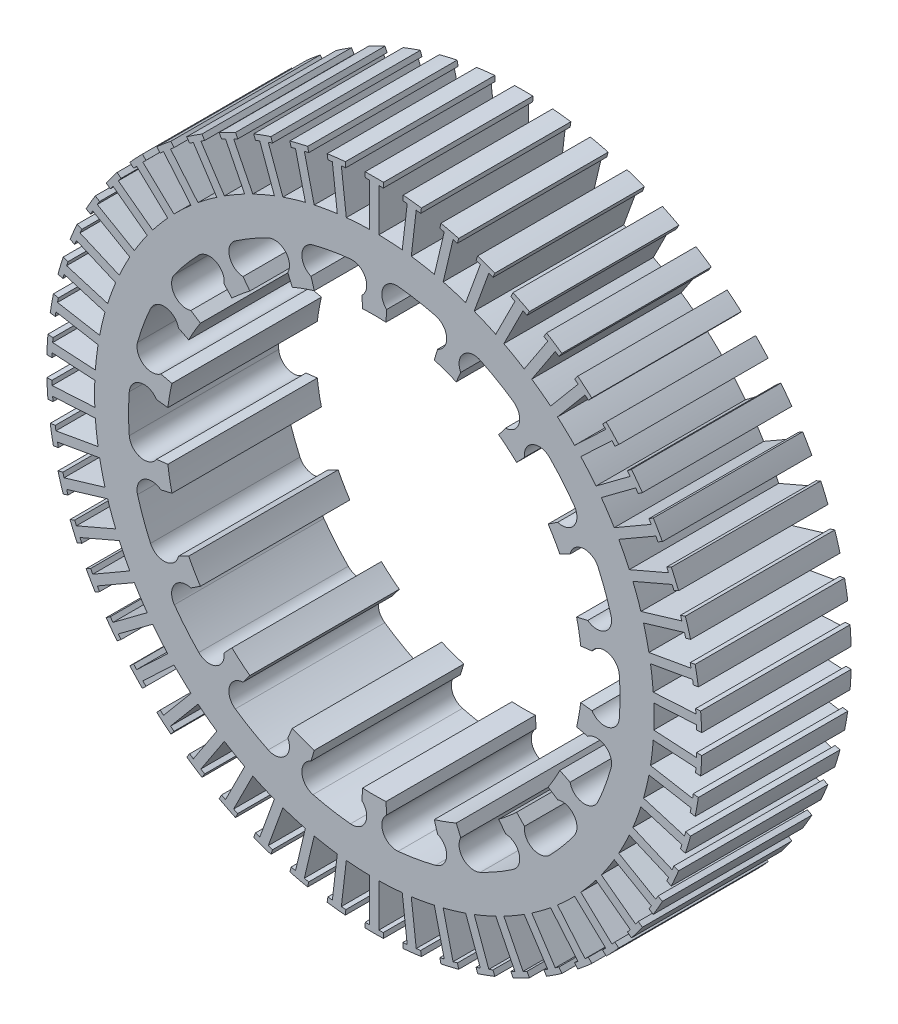
SolidWorks part; units mm, degrees
ref_plane "Front Plane" through (0, 0, 0) normal (0, 0, 1) x (1, 0, 0)
ref_plane "Top Plane" through (0, 0, 0) normal (0, 1, 0) x (1, 0, 0)
ref_plane "Right Plane" through (0, 0, 0) normal (1, 0, 0) x (0, 0, -1)
sketch "Sketch1" plane through (0, 0, 0) normal (0, 0, 1) x (1, 0, 0)
  line L0 (0, 0) -> (0, -32.4782) construction
  line L1 (0, 0) -> (-1.8282, -32.4267) construction
  line L2 (0, 0) -> (1.8282, -32.4267) construction
  line L3 (-1.5464, -27.4271) -> (1.5464, -27.4271) construction
  line L4 (1.5464, -27.4271) -> (1.6311, -28.9306)
  line L5 (-1.5464, -27.4271) -> (-1.6311, -28.9306)
  line L6 (0, 0) -> (-6.4192, -36.4052) construction
  line L7 (0, 0) -> (6.4192, -36.4052) construction
  line L8 (-3.2096, -18.2026) -> (3.2096, -18.2026) construction
  line L9 (-10.8337, -25.2441) -> (-11.4276, -26.628)
  line L10 (-7.9275, -26.3019) -> (-8.3621, -27.7438)
  line L11 (-18.8143, -20.0164) -> (-19.8458, -21.1137)
  line L12 (-16.4452, -22.0043) -> (-17.3467, -23.2106)
  line L13 (-24.5257, -12.3743) -> (-25.8702, -13.0527)
  line L14 (-22.9793, -15.0527) -> (-24.2391, -15.8779)
  line L15 (-27.2789, -3.2398) -> (-28.7743, -3.4174)
  line L16 (-26.7419, -6.2855) -> (-28.2079, -6.6301)
  line L17 (-26.7419, 6.2855) -> (-28.2079, 6.6301)
  line L18 (-27.2789, 3.2398) -> (-28.7743, 3.4174)
  line L19 (-22.9793, 15.0527) -> (-24.2391, 15.8779)
  line L20 (-24.5257, 12.3743) -> (-25.8702, 13.0527)
  line L21 (-16.4452, 22.0043) -> (-17.3467, 23.2106)
  line L22 (-18.8143, 20.0164) -> (-19.8458, 21.1137)
  line L23 (-7.9275, 26.3019) -> (-8.3621, 27.7438)
  line L24 (-10.8337, 25.2441) -> (-11.4276, 26.628)
  line L25 (1.5464, 27.4271) -> (1.6311, 28.9306)
  line L26 (-1.5464, 27.4271) -> (-1.6311, 28.9306)
  line L27 (10.8337, 25.2441) -> (11.4276, 26.628)
  line L28 (7.9275, 26.3019) -> (8.3621, 27.7438)
  line L29 (18.8143, 20.0164) -> (19.8458, 21.1137)
  line L30 (16.4452, 22.0043) -> (17.3467, 23.2106)
  line L31 (24.5257, 12.3743) -> (25.8702, 13.0527)
  line L32 (22.9793, 15.0527) -> (24.2391, 15.8779)
  line L33 (27.2789, 3.2398) -> (28.7743, 3.4174)
  line L34 (26.7419, 6.2855) -> (28.2079, 6.6301)
  line L35 (26.7419, -6.2855) -> (28.2079, -6.6301)
  line L36 (27.2789, -3.2398) -> (28.7743, -3.4174)
  line L37 (22.9793, -15.0527) -> (24.2391, -15.8779)
  line L38 (24.5257, -12.3743) -> (25.8702, -13.0527)
  line L39 (16.4452, -22.0043) -> (17.3467, -23.2106)
  line L40 (18.8143, -20.0164) -> (19.8458, -21.1137)
  line L41 (7.9275, -26.3019) -> (8.3621, -27.7438)
  line L42 (10.8337, -25.2441) -> (11.4276, -26.628)
  arc A0 (-1.5464, -27.4271) -> (1.5464, -27.4271) centre (0, 0) ccw construction
  arc A1 (-5.6398, -31.9848) -> (5.6398, -31.9848) centre (0, 0) ccw construction
  arc A3 (1.6311, -28.9306) -> (3.149, -32.3252) centre (2.9589, -30.3736) ccw
  arc A4 (-3.149, -32.3252) -> (-1.6311, -28.9306) centre (-2.9589, -30.3736) ccw
  arc A5 (1.5464, -27.4271) -> (-1.5464, -27.4271) centre (0, 0) cw
  circle A6 centre (0, 0) radius 36.9668
  arc A7 (3.149, -32.3252) -> (5.6398, -31.9848) centre (0, 0) ccw
  arc A8 (-5.6398, -31.9848) -> (-3.149, -32.3252) centre (0, 0) ccw
  arc A9 (-7.9275, -26.3019) -> (-10.8337, -25.2441) centre (0, 0) cw
  arc A10 (-8.3621, -27.7438) -> (-8.0967, -31.4528) centre (-7.6079, -29.5538) ccw
  arc A11 (-14.015, -29.2987) -> (-11.4276, -26.628) centre (-13.1688, -27.5298) ccw
  arc A12 (-16.2391, -28.127) -> (-14.015, -29.2987) centre (0, 0) ccw
  arc A13 (-8.0967, -31.4528) -> (-5.6398, -31.9848) centre (0, 0) ccw
  arc A14 (-16.4452, -22.0043) -> (-18.8143, -20.0164) centre (0, 0) cw
  arc A15 (-17.3467, -23.2106) -> (-18.3659, -26.7867) centre (-17.2571, -25.1694) ccw
  arc A16 (-23.1905, -22.7384) -> (-19.8458, -21.1137) centre (-21.7904, -21.3655) ccw
  arc A17 (-24.8798, -20.8766) -> (-23.1905, -22.7384) centre (0, 0) ccw
  arc A18 (-18.3659, -26.7867) -> (-16.2391, -28.127) centre (0, 0) ccw
  arc A19 (-22.9793, -15.0527) -> (-24.5257, -12.3743) centre (0, 0) cw
  arc A20 (-24.2391, -15.8779) -> (-26.4199, -18.8897) centre (-24.8248, -17.7493) ccw
  arc A21 (-29.569, -13.4355) -> (-25.8702, -13.0527) centre (-27.7837, -12.6243) ccw
  arc A22 (-30.5195, -11.1082) -> (-29.569, -13.4355) centre (0, 0) ccw
  arc A23 (-26.4199, -18.8897) -> (-24.8798, -20.8766) centre (0, 0) ccw
  arc A24 (-26.7419, -6.2855) -> (-27.2789, -3.2398) centre (0, 0) cw
  arc A25 (-28.2079, -6.6301) -> (-31.2873, -8.7144) centre (-29.3983, -8.1883) ccw
  arc A26 (-32.3809, -2.512) -> (-28.7743, -3.4174) centre (-30.4259, -2.3604) ccw
  arc A27 (-32.4782, 0) -> (-32.3809, -2.512) centre (0, 0) ccw
  arc A28 (-31.2873, -8.7144) -> (-30.5195, -11.1082) centre (0, 0) ccw
  arc A29 (-27.2789, 3.2398) -> (-26.7419, 6.2855) centre (0, 0) cw
  arc A30 (-28.7743, 3.4174) -> (-32.3809, 2.512) centre (-30.4259, 2.3604) ccw
  arc A31 (-31.2873, 8.7144) -> (-28.2079, 6.6301) centre (-29.3983, 8.1883) ccw
  arc A32 (-30.5195, 11.1082) -> (-31.2873, 8.7144) centre (0, 0) ccw
  arc A33 (-32.3809, 2.512) -> (-32.4782, 0) centre (0, 0) ccw
  arc A34 (-24.5257, 12.3743) -> (-22.9793, 15.0527) centre (0, 0) cw
  arc A35 (-25.8702, 13.0527) -> (-29.569, 13.4355) centre (-27.7837, 12.6243) ccw
  arc A36 (-26.4199, 18.8897) -> (-24.2391, 15.8779) centre (-24.8248, 17.7493) ccw
  arc A37 (-24.8798, 20.8766) -> (-26.4199, 18.8897) centre (0, 0) ccw
  arc A38 (-29.569, 13.4355) -> (-30.5195, 11.1082) centre (0, 0) ccw
  arc A39 (-18.8143, 20.0164) -> (-16.4452, 22.0043) centre (0, 0) cw
  arc A40 (-19.8458, 21.1137) -> (-23.1905, 22.7384) centre (-21.7904, 21.3655) ccw
  arc A41 (-18.3659, 26.7867) -> (-17.3467, 23.2106) centre (-17.2571, 25.1694) ccw
  arc A42 (-16.2391, 28.127) -> (-18.3659, 26.7867) centre (0, 0) ccw
  arc A43 (-23.1905, 22.7384) -> (-24.8798, 20.8766) centre (0, 0) ccw
  arc A44 (-10.8337, 25.2441) -> (-7.9275, 26.3019) centre (0, 0) cw
  arc A45 (-11.4276, 26.628) -> (-14.015, 29.2987) centre (-13.1688, 27.5298) ccw
  arc A46 (-8.0967, 31.4528) -> (-8.3621, 27.7438) centre (-7.6079, 29.5538) ccw
  arc A47 (-5.6398, 31.9848) -> (-8.0967, 31.4528) centre (0, 0) ccw
  arc A48 (-14.015, 29.2987) -> (-16.2391, 28.127) centre (0, 0) ccw
  arc A49 (-1.5464, 27.4271) -> (1.5464, 27.4271) centre (0, 0) cw
  arc A50 (-1.6311, 28.9306) -> (-3.149, 32.3252) centre (-2.9589, 30.3736) ccw
  arc A51 (3.149, 32.3252) -> (1.6311, 28.9306) centre (2.9589, 30.3736) ccw
  arc A52 (5.6398, 31.9848) -> (3.149, 32.3252) centre (0, 0) ccw
  arc A53 (-3.149, 32.3252) -> (-5.6398, 31.9848) centre (0, 0) ccw
  arc A54 (7.9275, 26.3019) -> (10.8337, 25.2441) centre (0, 0) cw
  arc A55 (8.3621, 27.7438) -> (8.0967, 31.4528) centre (7.6079, 29.5538) ccw
  arc A56 (14.015, 29.2987) -> (11.4276, 26.628) centre (13.1688, 27.5298) ccw
  arc A57 (16.2391, 28.127) -> (14.015, 29.2987) centre (0, 0) ccw
  arc A58 (8.0967, 31.4528) -> (5.6398, 31.9848) centre (0, 0) ccw
  arc A59 (16.4452, 22.0043) -> (18.8143, 20.0164) centre (0, 0) cw
  arc A60 (17.3467, 23.2106) -> (18.3659, 26.7867) centre (17.2571, 25.1694) ccw
  arc A61 (23.1905, 22.7384) -> (19.8458, 21.1137) centre (21.7904, 21.3655) ccw
  arc A62 (24.8798, 20.8766) -> (23.1905, 22.7384) centre (0, 0) ccw
  arc A63 (18.3659, 26.7867) -> (16.2391, 28.127) centre (0, 0) ccw
  arc A64 (22.9793, 15.0527) -> (24.5257, 12.3743) centre (0, 0) cw
  arc A65 (24.2391, 15.8779) -> (26.4199, 18.8897) centre (24.8248, 17.7493) ccw
  arc A66 (29.569, 13.4355) -> (25.8702, 13.0527) centre (27.7837, 12.6243) ccw
  arc A67 (30.5195, 11.1082) -> (29.569, 13.4355) centre (0, 0) ccw
  arc A68 (26.4199, 18.8897) -> (24.8798, 20.8766) centre (0, 0) ccw
  arc A69 (26.7419, 6.2855) -> (27.2789, 3.2398) centre (0, 0) cw
  arc A70 (28.2079, 6.6301) -> (31.2873, 8.7144) centre (29.3983, 8.1883) ccw
  arc A71 (32.3809, 2.512) -> (28.7743, 3.4174) centre (30.4259, 2.3604) ccw
  arc A72 (32.4782, 0) -> (32.3809, 2.512) centre (0, 0) ccw
  arc A73 (31.2873, 8.7144) -> (30.5195, 11.1082) centre (0, 0) ccw
  arc A74 (27.2789, -3.2398) -> (26.7419, -6.2855) centre (0, 0) cw
  arc A75 (28.7743, -3.4174) -> (32.3809, -2.512) centre (30.4259, -2.3604) ccw
  arc A76 (31.2873, -8.7144) -> (28.2079, -6.6301) centre (29.3983, -8.1883) ccw
  arc A77 (30.5195, -11.1082) -> (31.2873, -8.7144) centre (0, 0) ccw
  arc A78 (32.3809, -2.512) -> (32.4782, 0) centre (0, 0) ccw
  arc A79 (24.5257, -12.3743) -> (22.9793, -15.0527) centre (0, 0) cw
  arc A80 (25.8702, -13.0527) -> (29.569, -13.4355) centre (27.7837, -12.6243) ccw
  arc A81 (26.4199, -18.8897) -> (24.2391, -15.8779) centre (24.8248, -17.7493) ccw
  arc A82 (24.8798, -20.8766) -> (26.4199, -18.8897) centre (0, 0) ccw
  arc A83 (29.569, -13.4355) -> (30.5195, -11.1082) centre (0, 0) ccw
  arc A84 (18.8143, -20.0164) -> (16.4452, -22.0043) centre (0, 0) cw
  arc A85 (19.8458, -21.1137) -> (23.1905, -22.7384) centre (21.7904, -21.3655) ccw
  arc A86 (18.3659, -26.7867) -> (17.3467, -23.2106) centre (17.2571, -25.1694) ccw
  arc A87 (16.2391, -28.127) -> (18.3659, -26.7867) centre (0, 0) ccw
  arc A88 (23.1905, -22.7384) -> (24.8798, -20.8766) centre (0, 0) ccw
  arc A89 (10.8337, -25.2441) -> (7.9275, -26.3019) centre (0, 0) cw
  arc A90 (11.4276, -26.628) -> (14.015, -29.2987) centre (13.1688, -27.5298) ccw
  arc A91 (8.0967, -31.4528) -> (8.3621, -27.7438) centre (7.6079, -29.5538) ccw
  arc A92 (5.6398, -31.9848) -> (8.0967, -31.4528) centre (0, 0) ccw
  arc A93 (14.015, -29.2987) -> (16.2391, -28.127) centre (0, 0) ccw
  point P5 (-1.5464, -27.4271)
  point P7 (1.5464, -27.4271)
  point P14 (0, -27.4271)
  point P18 (0, 0)
  point P22 (0, -18.2026)
  point P25 (0, 0)
  point P197 (0, 0)
  dimension "D1" = 54.9412
  dimension "D2" = 64.9564
  dimension "D5" = 3.9218
  dimension "D6" = 73.9336
  dimension "D3" = 3.0927
  dimension "D4" = 1.506
  dimension "D7" = 20
  dimension "D8" = 18
extrude "Boss-Extrude1" add sketch "Sketch1" against normal blind 19.75 contours A6 A93 A90 L42 A89 L41 A91 A92 A7 A3 L4 A5 L5 A4 A8 A13 A10 L10 A9 L9 A11 A12 A18 A15 L12 A14 L11 A16 A17 A23 A20 L14 A19 L13 A21 A22 A28 A25 L16 A24 L15 A26 A27 A33 A30 L18 A29 L17 A31 A32 region at (-35.9212, 0, 0)
sketch "Sketch2" plane through (0, 0, 0) normal (0, 0, 1) x (1, 0, 0)
  line L0 (0, 0) -> (0, -42.6201) construction
  line L1 (0.5999, -36.9619) -> (0.5999, -42.6158)
  line L2 (-0.5999, -36.9619) -> (-0.5999, -42.6158)
  line L3 (0.5999, -39.2794) -> (-0.5999, -39.2794) construction
  line L4 (0, 0) -> (-1.2094, -43.273) construction
  line L5 (0, 0) -> (1.2094, -43.273) construction
  line L6 (-0.6047, -21.6365) -> (0.6047, -21.6365) construction
  line L7 (-1.2094, -43.273) -> (-1.1907, -42.6034)
  line L8 (1.1907, -42.6034) -> (1.2094, -43.273)
  line L9 (-1.2, -42.9382) -> (1.2, -42.9382) construction
  line L10 (-4.8869, -36.6423) -> (-5.5433, -42.258)
  line L11 (-3.6951, -36.7816) -> (-4.3515, -42.3973)
  line L12 (-6.2249, -42.84) -> (-6.1286, -42.1771)
  line L13 (-3.7633, -42.4536) -> (-3.8225, -43.1208)
  line L14 (-9.1078, -35.8272) -> (-10.4117, -41.3288)
  line L15 (-7.9402, -36.104) -> (-9.2441, -41.6055)
  line L16 (-11.1562, -41.8276) -> (-10.9836, -41.1805)
  line L17 (-8.6665, -41.7296) -> (-8.8027, -42.3854)
  line L18 (-13.2055, -34.5276) -> (-15.1392, -39.8406)
  line L19 (-12.078, -34.938) -> (-14.0117, -40.251)
  line L20 (-15.9367, -40.2496) -> (-15.6901, -39.6269)
  line L21 (-13.4524, -40.4414) -> (-13.6638, -41.0769)
  line L22 (-17.1246, -32.7611) -> (-19.6621, -37.8136)
  line L23 (-16.0523, -33.2996) -> (-18.5898, -38.3522)
  line L24 (-20.5016, -38.1274) -> (-20.1844, -37.5374)
  line L25 (-18.0564, -38.6062) -> (-18.3401, -39.2129)
  line L26 (-20.8122, -30.5515) -> (-23.919, -35.2753)
  line L27 (-19.8097, -31.2109) -> (-22.9165, -35.9347)
  line L28 (-24.7893, -35.4895) -> (-24.4058, -34.9404)
  line L29 (-22.4162, -36.2489) -> (-22.7685, -36.8186)
  line L30 (-24.2182, -27.9288) -> (-27.8525, -32.26)
  line L31 (-23.2991, -28.7001) -> (-26.9333, -33.0313)
  line L32 (-28.7418, -32.3716) -> (-28.2971, -31.8708)
  line L33 (-26.4728, -33.4015) -> (-26.8889, -33.9264)
  line L34 (-27.2968, -24.9284) -> (-31.4093, -28.8084)
  line L35 (-26.4734, -25.8012) -> (-30.5859, -29.6811)
  line L36 (-32.3055, -28.816) -> (-31.8057, -28.3702)
  line L37 (-30.1715, -30.1023) -> (-30.6457, -30.5754)
  line L38 (-30.0063, -21.5909) -> (-34.5414, -24.9672)
  line L39 (-29.2897, -22.5534) -> (-33.8249, -25.9296)
  line L40 (-35.4324, -24.8707) -> (-34.8842, -24.4859)
  line L41 (-33.4622, -26.3961) -> (-33.9881, -26.8109)
  line L42 (-32.3099, -17.9614) -> (-37.2064, -20.7883)
  line L43 (-31.71, -19.0005) -> (-36.6064, -21.8275)
  line L44 (-38.0802, -20.5891) -> (-37.491, -20.2706)
  line L45 (-36.3003, -22.3329) -> (-36.8708, -22.6838)
  line L46 (-34.1766, -14.089) -> (-39.3682, -16.3284)
  line L47 (-33.7014, -15.1907) -> (-38.8929, -17.4302)
  line L48 (-40.2129, -16.0291) -> (-39.5907, -15.7811)
  line L49 (-38.6475, -17.9676) -> (-39.2549, -18.25)
  line L50 (-35.5812, -10.0261) -> (-40.9976, -11.6476)
  line L51 (-35.2371, -11.1755) -> (-40.6535, -12.7971)
  line L52 (-41.8019, -11.2523) -> (-41.1551, -11.0782)
  line L53 (-40.4721, -13.3594) -> (-41.1082, -13.5694)
  line L54 (-36.5046, -5.8275) -> (-42.0726, -6.8093)
  line L55 (-36.2962, -7.0092) -> (-41.8642, -7.991)
  line L56 (-42.8256, -6.3233) -> (-42.1629, -6.2254)
  line L57 (-41.7494, -8.5706) -> (-42.4055, -8.7053)
  line L58 (-36.9343, -1.5502) -> (-42.5786, -1.879)
  line L59 (-36.8645, -2.7481) -> (-42.5089, -3.0768)
  line L60 (-43.2701, -1.3088) -> (-42.6006, -1.2885)
  line L61 (-42.4621, -3.6658) -> (-43.1294, -3.7234)
  line L62 (-36.8645, 2.7481) -> (-42.5089, 3.0768)
  line L63 (-36.9343, 1.5502) -> (-42.5786, 1.879)
  line L64 (-43.1294, 3.7234) -> (-42.4621, 3.6658)
  line L65 (-42.6006, 1.2885) -> (-43.2701, 1.3088)
  line L66 (-36.2962, 7.0092) -> (-41.8642, 7.991)
  line L67 (-36.5046, 5.8275) -> (-42.0726, 6.8093)
  line L68 (-42.4055, 8.7053) -> (-41.7494, 8.5706)
  line L69 (-42.1629, 6.2254) -> (-42.8256, 6.3233)
  line L70 (-35.2371, 11.1755) -> (-40.6535, 12.7971)
  line L71 (-35.5812, 10.0261) -> (-40.9976, 11.6476)
  line L72 (-41.1082, 13.5694) -> (-40.4721, 13.3594)
  line L73 (-41.1551, 11.0782) -> (-41.8019, 11.2523)
  line L74 (-33.7014, 15.1907) -> (-38.8929, 17.4302)
  line L75 (-34.1766, 14.089) -> (-39.3682, 16.3284)
  line L76 (-39.2549, 18.25) -> (-38.6475, 17.9676)
  line L77 (-39.5907, 15.7811) -> (-40.2129, 16.0291)
  line L78 (-31.71, 19.0005) -> (-36.6064, 21.8275)
  line L79 (-32.3099, 17.9614) -> (-37.2064, 20.7883)
  line L80 (-36.8708, 22.6838) -> (-36.3003, 22.3329)
  line L81 (-37.491, 20.2706) -> (-38.0802, 20.5891)
  line L82 (-29.2897, 22.5534) -> (-33.8249, 25.9296)
  line L83 (-30.0063, 21.5909) -> (-34.5414, 24.9672)
  line L84 (-33.9881, 26.8109) -> (-33.4622, 26.3961)
  line L85 (-34.8842, 24.4859) -> (-35.4324, 24.8707)
  line L86 (-26.4734, 25.8012) -> (-30.5859, 29.6811)
  line L87 (-27.2968, 24.9284) -> (-31.4093, 28.8084)
  line L88 (-30.6457, 30.5754) -> (-30.1715, 30.1023)
  line L89 (-31.8057, 28.3702) -> (-32.3055, 28.816)
  line L90 (-23.2991, 28.7001) -> (-26.9333, 33.0313)
  line L91 (-24.2182, 27.9288) -> (-27.8525, 32.26)
  line L92 (-26.8889, 33.9264) -> (-26.4728, 33.4015)
  line L93 (-28.2971, 31.8708) -> (-28.7418, 32.3716)
  line L94 (-19.8097, 31.2109) -> (-22.9165, 35.9347)
  line L95 (-20.8122, 30.5515) -> (-23.919, 35.2753)
  line L96 (-22.7685, 36.8186) -> (-22.4162, 36.2489)
  line L97 (-24.4058, 34.9404) -> (-24.7893, 35.4895)
  line L98 (-16.0523, 33.2996) -> (-18.5898, 38.3522)
  line L99 (-17.1246, 32.7611) -> (-19.6621, 37.8136)
  line L100 (-18.3401, 39.2129) -> (-18.0564, 38.6062)
  line L101 (-20.1844, 37.5374) -> (-20.5016, 38.1274)
  line L102 (-12.078, 34.938) -> (-14.0117, 40.251)
  line L103 (-13.2055, 34.5276) -> (-15.1392, 39.8406)
  line L104 (-13.6638, 41.0769) -> (-13.4524, 40.4414)
  line L105 (-15.6901, 39.6269) -> (-15.9367, 40.2496)
  line L106 (-7.9402, 36.104) -> (-9.2441, 41.6055)
  line L107 (-9.1078, 35.8272) -> (-10.4117, 41.3288)
  line L108 (-8.8027, 42.3854) -> (-8.6665, 41.7296)
  line L109 (-10.9836, 41.1805) -> (-11.1562, 41.8276)
  line L110 (-3.6951, 36.7816) -> (-4.3515, 42.3973)
  line L111 (-4.8869, 36.6423) -> (-5.5433, 42.258)
  line L112 (-3.8225, 43.1208) -> (-3.7633, 42.4536)
  line L113 (-6.1286, 42.1771) -> (-6.2249, 42.84)
  line L114 (0.5999, 36.9619) -> (0.5999, 42.6158)
  line L115 (-0.5999, 36.9619) -> (-0.5999, 42.6158)
  line L116 (1.2094, 43.273) -> (1.1907, 42.6034)
  line L117 (-1.1907, 42.6034) -> (-1.2094, 43.273)
  line L118 (4.8869, 36.6423) -> (5.5433, 42.258)
  line L119 (3.6951, 36.7816) -> (4.3515, 42.3973)
  line L120 (6.2249, 42.84) -> (6.1286, 42.1771)
  line L121 (3.7633, 42.4536) -> (3.8225, 43.1208)
  line L122 (9.1078, 35.8272) -> (10.4117, 41.3288)
  line L123 (7.9402, 36.104) -> (9.2441, 41.6055)
  line L124 (11.1562, 41.8276) -> (10.9836, 41.1805)
  line L125 (8.6665, 41.7296) -> (8.8027, 42.3854)
  line L126 (13.2055, 34.5276) -> (15.1392, 39.8406)
  line L127 (12.078, 34.938) -> (14.0117, 40.251)
  line L128 (15.9367, 40.2496) -> (15.6901, 39.6269)
  line L129 (13.4524, 40.4414) -> (13.6638, 41.0769)
  line L130 (17.1246, 32.7611) -> (19.6621, 37.8136)
  line L131 (16.0523, 33.2996) -> (18.5898, 38.3522)
  line L132 (20.5016, 38.1274) -> (20.1844, 37.5374)
  line L133 (18.0564, 38.6062) -> (18.3401, 39.2129)
  line L134 (20.8122, 30.5515) -> (23.919, 35.2753)
  line L135 (19.8097, 31.2109) -> (22.9165, 35.9347)
  line L136 (24.7893, 35.4895) -> (24.4058, 34.9404)
  line L137 (22.4162, 36.2489) -> (22.7685, 36.8186)
  line L138 (24.2182, 27.9288) -> (27.8525, 32.26)
  line L139 (23.2991, 28.7001) -> (26.9333, 33.0313)
  line L140 (28.7418, 32.3716) -> (28.2971, 31.8708)
  line L141 (26.4728, 33.4015) -> (26.8889, 33.9264)
  line L142 (27.2968, 24.9284) -> (31.4093, 28.8084)
  line L143 (26.4734, 25.8012) -> (30.5859, 29.6811)
  line L144 (32.3055, 28.816) -> (31.8057, 28.3702)
  line L145 (30.1715, 30.1023) -> (30.6457, 30.5754)
  line L146 (30.0063, 21.5909) -> (34.5414, 24.9672)
  line L147 (29.2897, 22.5534) -> (33.8249, 25.9296)
  line L148 (35.4324, 24.8707) -> (34.8842, 24.4859)
  line L149 (33.4622, 26.3961) -> (33.9881, 26.8109)
  line L150 (32.3099, 17.9614) -> (37.2064, 20.7883)
  line L151 (31.71, 19.0005) -> (36.6064, 21.8275)
  line L152 (38.0802, 20.5891) -> (37.491, 20.2706)
  line L153 (36.3003, 22.3329) -> (36.8708, 22.6838)
  line L154 (34.1766, 14.089) -> (39.3682, 16.3284)
  line L155 (33.7014, 15.1907) -> (38.8929, 17.4302)
  line L156 (40.2129, 16.0291) -> (39.5907, 15.7811)
  line L157 (38.6475, 17.9676) -> (39.2549, 18.25)
  line L158 (35.5812, 10.0261) -> (40.9976, 11.6476)
  line L159 (35.2371, 11.1755) -> (40.6535, 12.7971)
  line L160 (41.8019, 11.2523) -> (41.1551, 11.0782)
  line L161 (40.4721, 13.3594) -> (41.1082, 13.5694)
  line L162 (36.5046, 5.8275) -> (42.0726, 6.8093)
  line L163 (36.2962, 7.0092) -> (41.8642, 7.991)
  line L164 (42.8256, 6.3233) -> (42.1629, 6.2254)
  line L165 (41.7494, 8.5706) -> (42.4055, 8.7053)
  line L166 (36.9343, 1.5502) -> (42.5786, 1.879)
  line L167 (36.8645, 2.7481) -> (42.5089, 3.0768)
  line L168 (43.2701, 1.3088) -> (42.6006, 1.2885)
  line L169 (42.4621, 3.6658) -> (43.1294, 3.7234)
  line L170 (36.8645, -2.7481) -> (42.5089, -3.0768)
  line L171 (36.9343, -1.5502) -> (42.5786, -1.879)
  line L172 (43.1294, -3.7234) -> (42.4621, -3.6658)
  line L173 (42.6006, -1.2885) -> (43.2701, -1.3088)
  line L174 (36.2962, -7.0092) -> (41.8642, -7.991)
  line L175 (36.5046, -5.8275) -> (42.0726, -6.8093)
  line L176 (42.4055, -8.7053) -> (41.7494, -8.5706)
  line L177 (42.1629, -6.2254) -> (42.8256, -6.3233)
  line L178 (35.2371, -11.1755) -> (40.6535, -12.7971)
  line L179 (35.5812, -10.0261) -> (40.9976, -11.6476)
  line L180 (41.1082, -13.5694) -> (40.4721, -13.3594)
  line L181 (41.1551, -11.0782) -> (41.8019, -11.2523)
  line L182 (33.7014, -15.1907) -> (38.8929, -17.4302)
  line L183 (34.1766, -14.089) -> (39.3682, -16.3284)
  line L184 (39.2549, -18.25) -> (38.6475, -17.9676)
  line L185 (39.5907, -15.7811) -> (40.2129, -16.0291)
  line L186 (31.71, -19.0005) -> (36.6064, -21.8275)
  line L187 (32.3099, -17.9614) -> (37.2064, -20.7883)
  line L188 (36.8708, -22.6838) -> (36.3003, -22.3329)
  line L189 (37.491, -20.2706) -> (38.0802, -20.5891)
  line L190 (29.2897, -22.5534) -> (33.8249, -25.9296)
  line L191 (30.0063, -21.5909) -> (34.5414, -24.9672)
  line L192 (33.9881, -26.8109) -> (33.4622, -26.3961)
  line L193 (34.8842, -24.4859) -> (35.4324, -24.8707)
  line L194 (26.4734, -25.8012) -> (30.5859, -29.6811)
  line L195 (27.2968, -24.9284) -> (31.4093, -28.8084)
  line L196 (30.6457, -30.5754) -> (30.1715, -30.1023)
  line L197 (31.8057, -28.3702) -> (32.3055, -28.816)
  line L198 (23.2991, -28.7001) -> (26.9333, -33.0313)
  line L199 (24.2182, -27.9288) -> (27.8525, -32.26)
  line L200 (26.8889, -33.9264) -> (26.4728, -33.4015)
  line L201 (28.2971, -31.8708) -> (28.7418, -32.3716)
  line L202 (19.8097, -31.2109) -> (22.9165, -35.9347)
  line L203 (20.8122, -30.5515) -> (23.919, -35.2753)
  line L204 (22.7685, -36.8186) -> (22.4162, -36.2489)
  line L205 (24.4058, -34.9404) -> (24.7893, -35.4895)
  line L206 (16.0523, -33.2996) -> (18.5898, -38.3522)
  line L207 (17.1246, -32.7611) -> (19.6621, -37.8136)
  line L208 (18.3401, -39.2129) -> (18.0564, -38.6062)
  line L209 (20.1844, -37.5374) -> (20.5016, -38.1274)
  line L210 (12.078, -34.938) -> (14.0117, -40.251)
  line L211 (13.2055, -34.5276) -> (15.1392, -39.8406)
  line L212 (13.6638, -41.0769) -> (13.4524, -40.4414)
  line L213 (15.6901, -39.6269) -> (15.9367, -40.2496)
  line L214 (7.9402, -36.104) -> (9.2441, -41.6055)
  line L215 (9.1078, -35.8272) -> (10.4117, -41.3288)
  line L216 (8.8027, -42.3854) -> (8.6665, -41.7296)
  line L217 (10.9836, -41.1805) -> (11.1562, -41.8276)
  line L218 (3.6951, -36.7816) -> (4.3515, -42.3973)
  line L219 (4.8869, -36.6423) -> (5.5433, -42.258)
  line L220 (3.8225, -43.1208) -> (3.7633, -42.4536)
  line L221 (6.1286, -42.1771) -> (6.2249, -42.84)
  circle A0 centre (0, 0) radius 36.9668 construction
  arc A1 (-1.1907, -42.6034) -> (-0.5999, -42.6158) centre (0, 0) ccw
  arc A2 (-1.2094, -43.273) -> (1.2094, -43.273) centre (0, 0) ccw
  arc A3 (0.5999, -42.6158) -> (1.1907, -42.6034) centre (0, 0) ccw
  arc A4 (-4.3515, -42.3973) -> (-3.7633, -42.4536) centre (0, 0) ccw
  arc A5 (-6.1286, -42.1771) -> (-5.5433, -42.258) centre (0, 0) ccw
  arc A6 (-6.2249, -42.84) -> (-3.8225, -43.1208) centre (0, 0) ccw
  arc A7 (-9.2441, -41.6055) -> (-8.6665, -41.7296) centre (0, 0) ccw
  arc A8 (-10.9836, -41.1805) -> (-10.4117, -41.3288) centre (0, 0) ccw
  arc A9 (-11.1562, -41.8276) -> (-8.8027, -42.3854) centre (0, 0) ccw
  arc A10 (-14.0117, -40.251) -> (-13.4524, -40.4414) centre (0, 0) ccw
  arc A11 (-15.6901, -39.6269) -> (-15.1392, -39.8406) centre (0, 0) ccw
  arc A12 (-15.9367, -40.2496) -> (-13.6638, -41.0769) centre (0, 0) ccw
  arc A13 (-18.5898, -38.3522) -> (-18.0564, -38.6062) centre (0, 0) ccw
  arc A14 (-20.1844, -37.5374) -> (-19.6621, -37.8136) centre (0, 0) ccw
  arc A15 (-20.5016, -38.1274) -> (-18.3401, -39.2129) centre (0, 0) ccw
  arc A16 (-22.9165, -35.9347) -> (-22.4162, -36.2489) centre (0, 0) ccw
  arc A17 (-24.4058, -34.9404) -> (-23.919, -35.2753) centre (0, 0) ccw
  arc A18 (-24.7893, -35.4895) -> (-22.7685, -36.8186) centre (0, 0) ccw
  arc A19 (-26.9333, -33.0313) -> (-26.4728, -33.4015) centre (0, 0) ccw
  arc A20 (-28.2971, -31.8708) -> (-27.8525, -32.26) centre (0, 0) ccw
  arc A21 (-28.7418, -32.3716) -> (-26.8889, -33.9264) centre (0, 0) ccw
  arc A22 (-30.5859, -29.6811) -> (-30.1715, -30.1023) centre (0, 0) ccw
  arc A23 (-31.8057, -28.3702) -> (-31.4093, -28.8084) centre (0, 0) ccw
  arc A24 (-32.3055, -28.816) -> (-30.6457, -30.5754) centre (0, 0) ccw
  arc A25 (-33.8249, -25.9296) -> (-33.4622, -26.3961) centre (0, 0) ccw
  arc A26 (-34.8842, -24.4859) -> (-34.5414, -24.9672) centre (0, 0) ccw
  arc A27 (-35.4324, -24.8707) -> (-33.9881, -26.8109) centre (0, 0) ccw
  arc A28 (-36.6064, -21.8275) -> (-36.3003, -22.3329) centre (0, 0) ccw
  arc A29 (-37.491, -20.2706) -> (-37.2064, -20.7883) centre (0, 0) ccw
  arc A30 (-38.0802, -20.5891) -> (-36.8708, -22.6838) centre (0, 0) ccw
  arc A31 (-38.8929, -17.4302) -> (-38.6475, -17.9676) centre (0, 0) ccw
  arc A32 (-39.5907, -15.7811) -> (-39.3682, -16.3284) centre (0, 0) ccw
  arc A33 (-40.2129, -16.0291) -> (-39.2549, -18.25) centre (0, 0) ccw
  arc A34 (-40.6535, -12.7971) -> (-40.4721, -13.3594) centre (0, 0) ccw
  arc A35 (-41.1551, -11.0782) -> (-40.9976, -11.6476) centre (0, 0) ccw
  arc A36 (-41.8019, -11.2523) -> (-41.1082, -13.5694) centre (0, 0) ccw
  arc A37 (-41.8642, -7.991) -> (-41.7494, -8.5706) centre (0, 0) ccw
  arc A38 (-42.1629, -6.2254) -> (-42.0726, -6.8093) centre (0, 0) ccw
  arc A39 (-42.8256, -6.3233) -> (-42.4055, -8.7053) centre (0, 0) ccw
  arc A40 (-42.5089, -3.0768) -> (-42.4621, -3.6658) centre (0, 0) ccw
  arc A41 (-42.6006, -1.2885) -> (-42.5786, -1.879) centre (0, 0) ccw
  arc A42 (-43.2701, -1.3088) -> (-43.1294, -3.7234) centre (0, 0) ccw
  arc A43 (-42.5786, 1.879) -> (-42.6006, 1.2885) centre (0, 0) ccw
  arc A44 (-42.4621, 3.6658) -> (-42.5089, 3.0768) centre (0, 0) ccw
  arc A45 (-43.1294, 3.7234) -> (-43.2701, 1.3088) centre (0, 0) ccw
  arc A46 (-42.0726, 6.8093) -> (-42.1629, 6.2254) centre (0, 0) ccw
  arc A47 (-41.7494, 8.5706) -> (-41.8642, 7.991) centre (0, 0) ccw
  arc A48 (-42.4055, 8.7053) -> (-42.8256, 6.3233) centre (0, 0) ccw
  arc A49 (-40.9976, 11.6476) -> (-41.1551, 11.0782) centre (0, 0) ccw
  arc A50 (-40.4721, 13.3594) -> (-40.6535, 12.7971) centre (0, 0) ccw
  arc A51 (-41.1082, 13.5694) -> (-41.8019, 11.2523) centre (0, 0) ccw
  arc A52 (-39.3682, 16.3284) -> (-39.5907, 15.7811) centre (0, 0) ccw
  arc A53 (-38.6475, 17.9676) -> (-38.8929, 17.4302) centre (0, 0) ccw
  arc A54 (-39.2549, 18.25) -> (-40.2129, 16.0291) centre (0, 0) ccw
  arc A55 (-37.2064, 20.7883) -> (-37.491, 20.2706) centre (0, 0) ccw
  arc A56 (-36.3003, 22.3329) -> (-36.6064, 21.8275) centre (0, 0) ccw
  arc A57 (-36.8708, 22.6838) -> (-38.0802, 20.5891) centre (0, 0) ccw
  arc A58 (-34.5414, 24.9672) -> (-34.8842, 24.4859) centre (0, 0) ccw
  arc A59 (-33.4622, 26.3961) -> (-33.8249, 25.9296) centre (0, 0) ccw
  arc A60 (-33.9881, 26.8109) -> (-35.4324, 24.8707) centre (0, 0) ccw
  arc A61 (-31.4093, 28.8084) -> (-31.8057, 28.3702) centre (0, 0) ccw
  arc A62 (-30.1715, 30.1023) -> (-30.5859, 29.6811) centre (0, 0) ccw
  arc A63 (-30.6457, 30.5754) -> (-32.3055, 28.816) centre (0, 0) ccw
  arc A64 (-27.8525, 32.26) -> (-28.2971, 31.8708) centre (0, 0) ccw
  arc A65 (-26.4728, 33.4015) -> (-26.9333, 33.0313) centre (0, 0) ccw
  arc A66 (-26.8889, 33.9264) -> (-28.7418, 32.3716) centre (0, 0) ccw
  arc A67 (-23.919, 35.2753) -> (-24.4058, 34.9404) centre (0, 0) ccw
  arc A68 (-22.4162, 36.2489) -> (-22.9165, 35.9347) centre (0, 0) ccw
  arc A69 (-22.7685, 36.8186) -> (-24.7893, 35.4895) centre (0, 0) ccw
  arc A70 (-19.6621, 37.8136) -> (-20.1844, 37.5374) centre (0, 0) ccw
  arc A71 (-18.0564, 38.6062) -> (-18.5898, 38.3522) centre (0, 0) ccw
  arc A72 (-18.3401, 39.2129) -> (-20.5016, 38.1274) centre (0, 0) ccw
  arc A73 (-15.1392, 39.8406) -> (-15.6901, 39.6269) centre (0, 0) ccw
  arc A74 (-13.4524, 40.4414) -> (-14.0117, 40.251) centre (0, 0) ccw
  arc A75 (-13.6638, 41.0769) -> (-15.9367, 40.2496) centre (0, 0) ccw
  arc A76 (-10.4117, 41.3288) -> (-10.9836, 41.1805) centre (0, 0) ccw
  arc A77 (-8.6665, 41.7296) -> (-9.2441, 41.6055) centre (0, 0) ccw
  arc A78 (-8.8027, 42.3854) -> (-11.1562, 41.8276) centre (0, 0) ccw
  arc A79 (-5.5433, 42.258) -> (-6.1286, 42.1771) centre (0, 0) ccw
  arc A80 (-3.7633, 42.4536) -> (-4.3515, 42.3973) centre (0, 0) ccw
  arc A81 (-3.8225, 43.1208) -> (-6.2249, 42.84) centre (0, 0) ccw
  arc A82 (-0.5999, 42.6158) -> (-1.1907, 42.6034) centre (0, 0) ccw
  arc A83 (1.1907, 42.6034) -> (0.5999, 42.6158) centre (0, 0) ccw
  arc A84 (1.2094, 43.273) -> (-1.2094, 43.273) centre (0, 0) ccw
  arc A85 (4.3515, 42.3973) -> (3.7633, 42.4536) centre (0, 0) ccw
  arc A86 (6.1286, 42.1771) -> (5.5433, 42.258) centre (0, 0) ccw
  arc A87 (6.2249, 42.84) -> (3.8225, 43.1208) centre (0, 0) ccw
  arc A88 (9.2441, 41.6055) -> (8.6665, 41.7296) centre (0, 0) ccw
  arc A89 (10.9836, 41.1805) -> (10.4117, 41.3288) centre (0, 0) ccw
  arc A90 (11.1562, 41.8276) -> (8.8027, 42.3854) centre (0, 0) ccw
  arc A91 (14.0117, 40.251) -> (13.4524, 40.4414) centre (0, 0) ccw
  arc A92 (15.6901, 39.6269) -> (15.1392, 39.8406) centre (0, 0) ccw
  arc A93 (15.9367, 40.2496) -> (13.6638, 41.0769) centre (0, 0) ccw
  arc A94 (18.5898, 38.3522) -> (18.0564, 38.6062) centre (0, 0) ccw
  arc A95 (20.1844, 37.5374) -> (19.6621, 37.8136) centre (0, 0) ccw
  arc A96 (20.5016, 38.1274) -> (18.3401, 39.2129) centre (0, 0) ccw
  arc A97 (22.9165, 35.9347) -> (22.4162, 36.2489) centre (0, 0) ccw
  arc A98 (24.4058, 34.9404) -> (23.919, 35.2753) centre (0, 0) ccw
  arc A99 (24.7893, 35.4895) -> (22.7685, 36.8186) centre (0, 0) ccw
  arc A100 (26.9333, 33.0313) -> (26.4728, 33.4015) centre (0, 0) ccw
  arc A101 (28.2971, 31.8708) -> (27.8525, 32.26) centre (0, 0) ccw
  arc A102 (28.7418, 32.3716) -> (26.8889, 33.9264) centre (0, 0) ccw
  arc A103 (30.5859, 29.6811) -> (30.1715, 30.1023) centre (0, 0) ccw
  arc A104 (31.8057, 28.3702) -> (31.4093, 28.8084) centre (0, 0) ccw
  arc A105 (32.3055, 28.816) -> (30.6457, 30.5754) centre (0, 0) ccw
  arc A106 (33.8249, 25.9296) -> (33.4622, 26.3961) centre (0, 0) ccw
  arc A107 (34.8842, 24.4859) -> (34.5414, 24.9672) centre (0, 0) ccw
  arc A108 (35.4324, 24.8707) -> (33.9881, 26.8109) centre (0, 0) ccw
  arc A109 (36.6064, 21.8275) -> (36.3003, 22.3329) centre (0, 0) ccw
  arc A110 (37.491, 20.2706) -> (37.2064, 20.7883) centre (0, 0) ccw
  arc A111 (38.0802, 20.5891) -> (36.8708, 22.6838) centre (0, 0) ccw
  arc A112 (38.8929, 17.4302) -> (38.6475, 17.9676) centre (0, 0) ccw
  arc A113 (39.5907, 15.7811) -> (39.3682, 16.3284) centre (0, 0) ccw
  arc A114 (40.2129, 16.0291) -> (39.2549, 18.25) centre (0, 0) ccw
  arc A115 (40.6535, 12.7971) -> (40.4721, 13.3594) centre (0, 0) ccw
  arc A116 (41.1551, 11.0782) -> (40.9976, 11.6476) centre (0, 0) ccw
  arc A117 (41.8019, 11.2523) -> (41.1082, 13.5694) centre (0, 0) ccw
  arc A118 (41.8642, 7.991) -> (41.7494, 8.5706) centre (0, 0) ccw
  arc A119 (42.1629, 6.2254) -> (42.0726, 6.8093) centre (0, 0) ccw
  arc A120 (42.8256, 6.3233) -> (42.4055, 8.7053) centre (0, 0) ccw
  arc A121 (42.5089, 3.0768) -> (42.4621, 3.6658) centre (0, 0) ccw
  arc A122 (42.6006, 1.2885) -> (42.5786, 1.879) centre (0, 0) ccw
  arc A123 (43.2701, 1.3088) -> (43.1294, 3.7234) centre (0, 0) ccw
  arc A124 (42.5786, -1.879) -> (42.6006, -1.2885) centre (0, 0) ccw
  arc A125 (42.4621, -3.6658) -> (42.5089, -3.0768) centre (0, 0) ccw
  arc A126 (43.1294, -3.7234) -> (43.2701, -1.3088) centre (0, 0) ccw
  arc A127 (42.0726, -6.8093) -> (42.1629, -6.2254) centre (0, 0) ccw
  arc A128 (41.7494, -8.5706) -> (41.8642, -7.991) centre (0, 0) ccw
  arc A129 (42.4055, -8.7053) -> (42.8256, -6.3233) centre (0, 0) ccw
  arc A130 (40.9976, -11.6476) -> (41.1551, -11.0782) centre (0, 0) ccw
  arc A131 (40.4721, -13.3594) -> (40.6535, -12.7971) centre (0, 0) ccw
  arc A132 (41.1082, -13.5694) -> (41.8019, -11.2523) centre (0, 0) ccw
  arc A133 (39.3682, -16.3284) -> (39.5907, -15.7811) centre (0, 0) ccw
  arc A134 (38.6475, -17.9676) -> (38.8929, -17.4302) centre (0, 0) ccw
  arc A135 (39.2549, -18.25) -> (40.2129, -16.0291) centre (0, 0) ccw
  arc A136 (37.2064, -20.7883) -> (37.491, -20.2706) centre (0, 0) ccw
  arc A137 (36.3003, -22.3329) -> (36.6064, -21.8275) centre (0, 0) ccw
  arc A138 (36.8708, -22.6838) -> (38.0802, -20.5891) centre (0, 0) ccw
  arc A139 (34.5414, -24.9672) -> (34.8842, -24.4859) centre (0, 0) ccw
  arc A140 (33.4622, -26.3961) -> (33.8249, -25.9296) centre (0, 0) ccw
  arc A141 (33.9881, -26.8109) -> (35.4324, -24.8707) centre (0, 0) ccw
  arc A142 (31.4093, -28.8084) -> (31.8057, -28.3702) centre (0, 0) ccw
  arc A143 (30.1715, -30.1023) -> (30.5859, -29.6811) centre (0, 0) ccw
  arc A144 (30.6457, -30.5754) -> (32.3055, -28.816) centre (0, 0) ccw
  arc A145 (27.8525, -32.26) -> (28.2971, -31.8708) centre (0, 0) ccw
  arc A146 (26.4728, -33.4015) -> (26.9333, -33.0313) centre (0, 0) ccw
  arc A147 (26.8889, -33.9264) -> (28.7418, -32.3716) centre (0, 0) ccw
  arc A148 (23.919, -35.2753) -> (24.4058, -34.9404) centre (0, 0) ccw
  arc A149 (22.4162, -36.2489) -> (22.9165, -35.9347) centre (0, 0) ccw
  arc A150 (22.7685, -36.8186) -> (24.7893, -35.4895) centre (0, 0) ccw
  arc A151 (19.6621, -37.8136) -> (20.1844, -37.5374) centre (0, 0) ccw
  arc A152 (18.0564, -38.6062) -> (18.5898, -38.3522) centre (0, 0) ccw
  arc A153 (18.3401, -39.2129) -> (20.5016, -38.1274) centre (0, 0) ccw
  arc A154 (15.1392, -39.8406) -> (15.6901, -39.6269) centre (0, 0) ccw
  arc A155 (13.4524, -40.4414) -> (14.0117, -40.251) centre (0, 0) ccw
  arc A156 (13.6638, -41.0769) -> (15.9367, -40.2496) centre (0, 0) ccw
  arc A157 (10.4117, -41.3288) -> (10.9836, -41.1805) centre (0, 0) ccw
  arc A158 (8.6665, -41.7296) -> (9.2441, -41.6055) centre (0, 0) ccw
  arc A159 (8.8027, -42.3854) -> (11.1562, -41.8276) centre (0, 0) ccw
  arc A160 (5.5433, -42.258) -> (6.1286, -42.1771) centre (0, 0) ccw
  arc A161 (3.7633, -42.4536) -> (4.3515, -42.3973) centre (0, 0) ccw
  arc A162 (3.8225, -43.1208) -> (6.2249, -42.84) centre (0, 0) ccw
  arc A163 (0.5999, -36.9619) -> (3.6951, -36.7816) centre (0, 0) ccw
  arc A164 (-3.6951, -36.7816) -> (-0.5999, -36.9619) centre (0, 0) ccw
  arc A165 (-7.9402, -36.104) -> (-4.8869, -36.6423) centre (0, 0) ccw
  arc A166 (-12.078, -34.938) -> (-9.1078, -35.8272) centre (0, 0) ccw
  arc A167 (-16.0523, -33.2996) -> (-13.2055, -34.5276) centre (0, 0) ccw
  arc A168 (-19.8097, -31.2109) -> (-17.1246, -32.7611) centre (0, 0) ccw
  arc A169 (-23.2991, -28.7001) -> (-20.8122, -30.5515) centre (0, 0) ccw
  arc A170 (-26.4734, -25.8012) -> (-24.2182, -27.9288) centre (0, 0) ccw
  arc A171 (-29.2897, -22.5534) -> (-27.2968, -24.9284) centre (0, 0) ccw
  arc A172 (-31.71, -19.0005) -> (-30.0063, -21.5909) centre (0, 0) ccw
  arc A173 (-33.7014, -15.1907) -> (-32.3099, -17.9614) centre (0, 0) ccw
  arc A174 (-35.2371, -11.1755) -> (-34.1766, -14.089) centre (0, 0) ccw
  arc A175 (-36.2962, -7.0092) -> (-35.5812, -10.0261) centre (0, 0) ccw
  arc A176 (-36.8645, -2.7481) -> (-36.5046, -5.8275) centre (0, 0) ccw
  arc A177 (-36.9343, 1.5502) -> (-36.9343, -1.5502) centre (0, 0) ccw
  arc A178 (-36.5046, 5.8275) -> (-36.8645, 2.7481) centre (0, 0) ccw
  arc A179 (-35.5812, 10.0261) -> (-36.2962, 7.0092) centre (0, 0) ccw
  arc A180 (-34.1766, 14.089) -> (-35.2371, 11.1755) centre (0, 0) ccw
  arc A181 (-32.3099, 17.9614) -> (-33.7014, 15.1907) centre (0, 0) ccw
  arc A182 (-30.0063, 21.5909) -> (-31.71, 19.0005) centre (0, 0) ccw
  arc A183 (-27.2968, 24.9284) -> (-29.2897, 22.5534) centre (0, 0) ccw
  arc A184 (-24.2182, 27.9288) -> (-26.4734, 25.8012) centre (0, 0) ccw
  arc A185 (-20.8122, 30.5515) -> (-23.2991, 28.7001) centre (0, 0) ccw
  arc A186 (-17.1246, 32.7611) -> (-19.8097, 31.2109) centre (0, 0) ccw
  arc A187 (-13.2055, 34.5276) -> (-16.0523, 33.2996) centre (0, 0) ccw
  arc A188 (-9.1078, 35.8272) -> (-12.078, 34.938) centre (0, 0) ccw
  arc A189 (-4.8869, 36.6423) -> (-7.9402, 36.104) centre (0, 0) ccw
  arc A190 (-0.5999, 36.9619) -> (-3.6951, 36.7816) centre (0, 0) ccw
  arc A191 (3.6951, 36.7816) -> (0.5999, 36.9619) centre (0, 0) ccw
  arc A192 (7.9402, 36.104) -> (4.8869, 36.6423) centre (0, 0) ccw
  arc A193 (12.078, 34.938) -> (9.1078, 35.8272) centre (0, 0) ccw
  arc A194 (16.0523, 33.2996) -> (13.2055, 34.5276) centre (0, 0) ccw
  arc A195 (19.8097, 31.2109) -> (17.1246, 32.7611) centre (0, 0) ccw
  arc A196 (23.2991, 28.7001) -> (20.8122, 30.5515) centre (0, 0) ccw
  arc A197 (26.4734, 25.8012) -> (24.2182, 27.9288) centre (0, 0) ccw
  arc A198 (29.2897, 22.5534) -> (27.2968, 24.9284) centre (0, 0) ccw
  arc A199 (31.71, 19.0005) -> (30.0063, 21.5909) centre (0, 0) ccw
  arc A200 (33.7014, 15.1907) -> (32.3099, 17.9614) centre (0, 0) ccw
  arc A201 (35.2371, 11.1755) -> (34.1766, 14.089) centre (0, 0) ccw
  arc A202 (36.2962, 7.0092) -> (35.5812, 10.0261) centre (0, 0) ccw
  arc A203 (36.8645, 2.7481) -> (36.5046, 5.8275) centre (0, 0) ccw
  arc A204 (36.9343, -1.5502) -> (36.9343, 1.5502) centre (0, 0) ccw
  arc A205 (36.5046, -5.8275) -> (36.8645, -2.7481) centre (0, 0) ccw
  arc A206 (35.5812, -10.0261) -> (36.2962, -7.0092) centre (0, 0) ccw
  arc A207 (34.1766, -14.089) -> (35.2371, -11.1755) centre (0, 0) ccw
  arc A208 (32.3099, -17.9614) -> (33.7014, -15.1907) centre (0, 0) ccw
  arc A209 (30.0063, -21.5909) -> (31.71, -19.0005) centre (0, 0) ccw
  arc A210 (27.2968, -24.9284) -> (29.2897, -22.5534) centre (0, 0) ccw
  arc A211 (24.2182, -27.9288) -> (26.4734, -25.8012) centre (0, 0) ccw
  arc A212 (20.8122, -30.5515) -> (23.2991, -28.7001) centre (0, 0) ccw
  arc A213 (17.1246, -32.7611) -> (19.8097, -31.2109) centre (0, 0) ccw
  arc A214 (13.2055, -34.5276) -> (16.0523, -33.2996) centre (0, 0) ccw
  arc A215 (9.1078, -35.8272) -> (12.078, -34.938) centre (0, 0) ccw
  arc A216 (4.8869, -36.6423) -> (7.9402, -36.104) centre (0, 0) ccw
  circle A217 centre (0, 0) radius 36.9668 construction
  circle A218 centre (0, 0) radius 32.4782
  point P11 (0, -39.2794)
  point P17 (0, -21.6365)
  point P447 (0, 0)
  point P555 (0, 0)
  dimension "D1" = 5.6533
  dimension "D3" = 0.6698
  dimension "D2" = 1.1999
  dimension "D4" = 2.4
  dimension "D5" = 54
  dimension "D6" = 54
extrude "Boss-Extrude2" add sketch "Sketch2" against normal up to surface (19.75 mm away) up to face at (0, 0, -19.75)
